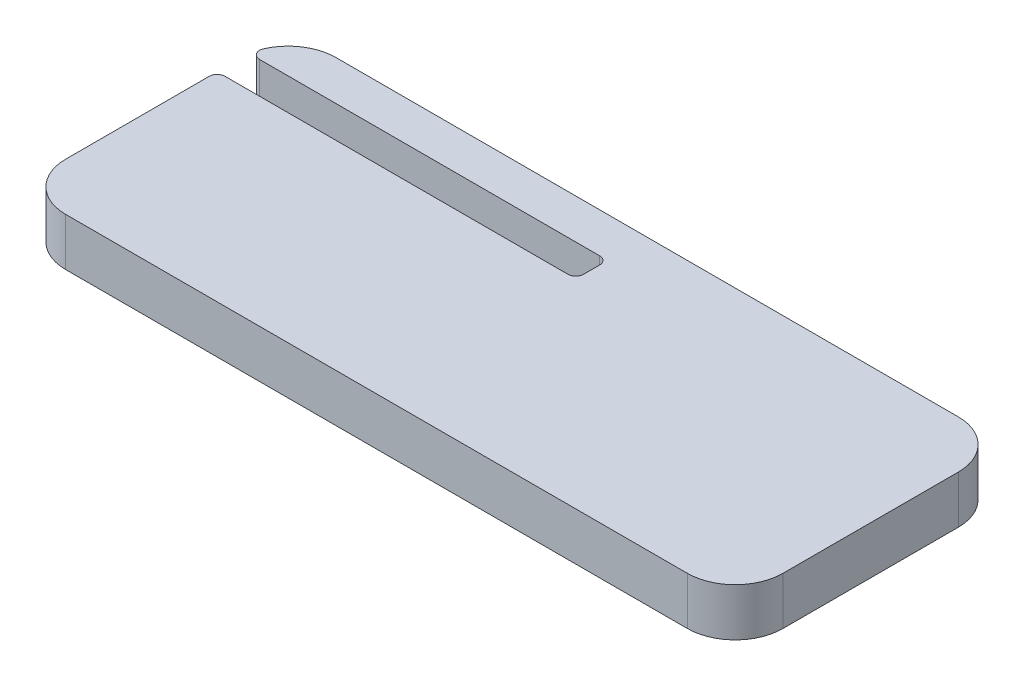
SolidWorks part; units mm, degrees
ref_plane "Alzado" through (0, 0, 0) normal (0, 0, 1) x (1, 0, 0)
ref_plane "Planta" through (0, 0, 0) normal (0, 1, 0) x (1, 0, 0)
ref_plane "Vista lateral" through (0, 0, 0) normal (1, 0, 0) x (0, 0, -1)
sketch "Croquis1" plane through (0, 0, 0) normal (0, 1, 0) x (1, 0, 0)
  line L5 (-22.5, 9.9298) -> (22.5, 9.9298)
  line L6 (-22.5, 9.9298) -> (-22.5, -7.0702)
  line L7 (-22.5, -7.0702) -> (22.5, -7.0702)
  line L8 (22.5, 9.9298) -> (22.5, -7.0702)
  dimension "D1" = 9.9298
  dimension "D2" = 22.5
  dimension "D3" = 17
  dimension "D4" = 45
extrude "Saliente-Extruir1" add sketch "Croquis1" along normal blind 3
sketch "Croquis2" plane through (0, 3, 0) normal (0, 1, 0) x (1, 0, 0)
  line L0 (-22.5, 9.9298) -> (-22.5, -7.0702) construction
  line L1 (-22.5, 7.4298) -> (0, 7.4298)
  line L2 (-22.5, 7.4298) -> (-22.5, 5.4298)
  line L3 (-22.5, 5.4298) -> (0, 5.4298)
  line L4 (0, 7.4298) -> (0, 5.4298)
  line L6 (22.5, 9.9298) -> (-22.5, 9.9298) construction
  dimension "D1" = 22.5
  dimension "D2" = 2.5
  dimension "D3" = 2
extrude "Cortar-Extruir1" cut sketch "Croquis2" against normal up to surface (3 mm away) up to face at (0, 0, -1.4298)
fillet "Redondeo1" radius 3 4 edges at (-22.5, 1.5, 7.0702) (-22.5, 1.5, -9.9298) (22.5, 1.5, 7.0702) (22.5, 1.5, -9.9298)
fillet "Redondeo4" radius 0.5 4 edges at (-22.5, 1.5, -5.4298) (0, 1.5, -5.4298) (0, 1.5, -7.4298) (-22.5, 1.5, -7.4298)
